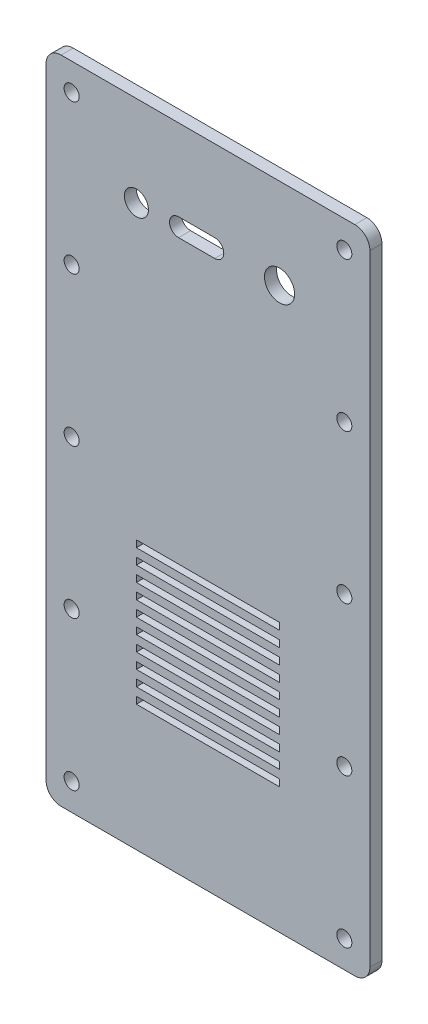
SolidWorks part; units mm, degrees
ref_plane "Front Plane" through (0, 0, 0) normal (0, 0, 1) x (1, 0, 0)
ref_plane "Top Plane" through (0, 0, 0) normal (0, 1, 0) x (1, 0, 0)
ref_plane "Right Plane" through (0, 0, 0) normal (1, 0, 0) x (0, 0, -1)
sketch "Sketch1" plane through (0, 0, 0) normal (0, 0, 1) x (1, 0, 0)
  line L1 (-17.88, -45) -> (17.88, -45) construction
  line L2 (-17.88, -45) -> (-17.88, 45) construction
  line L3 (-17.88, 45) -> (17.88, 45) construction
  line L4 (17.88, -45) -> (17.88, 45) construction
  line L5 (-17.88, -45) -> (17.88, 45) construction
  line L6 (-17.88, 45) -> (17.88, -45) construction
  line L7 (-26.88, 54) -> (26.88, 54)
  line L8 (-26.88, 54) -> (-26.88, -54)
  line L9 (-26.88, -54) -> (26.88, -54)
  line L10 (26.88, 54) -> (26.88, -54)
  line L11 (-26.88, 54) -> (26.88, -54) construction
  line L12 (-26.88, -54) -> (26.88, 54) construction
  point P0 (0, 0)
  point P6 (0, 0)
  dimension "D1" = 90
  dimension "D2" = 35.76
  dimension "D3" = 9
  dimension "D4" = 9
extrude "Boss-Extrude1" add sketch "Sketch1" along normal blind 2
fillet "Fillet1" radius 2.5 4 edges at (-26.88, -54, 1) (26.88, -54, 1) (-26.88, 54, 1) (26.88, 54, 1)
sketch "Sketch2" plane through (0, 0, 2) normal (0, 0, 1) x (1, 0, 0)
  line L0 (-17.88, -45) -> (-17.88, 45) construction
  line L1 (-22.63, -49.5) -> (22.63, -49.5) construction
  line L2 (-22.63, -49.5) -> (-22.63, 49.5) construction
  line L3 (-22.63, 49.5) -> (22.63, 49.5) construction
  line L4 (22.63, -49.5) -> (22.63, 49.5) construction
  line L5 (-22.63, -49.5) -> (22.63, 49.5) construction
  line L6 (-22.63, 49.5) -> (22.63, -49.5) construction
  circle A0 centre (-22.63, 49.5) radius 1.25
  circle A1 centre (22.63, 49.5) radius 1.25
  circle A2 centre (22.63, 24.75) radius 1.25
  circle A3 centre (22.63, 0) radius 1.25
  circle A4 centre (22.63, -24.75) radius 1.25
  circle A5 centre (22.63, -49.5) radius 1.25
  circle A6 centre (-22.63, 24.75) radius 1.25
  circle A7 centre (-22.63, 0) radius 1.25
  circle A8 centre (-22.63, -24.75) radius 1.25
  circle A9 centre (-22.63, -49.5) radius 1.25
  point P0 (0, 0)
  dimension "D3" = 2.5
  dimension "D1" = 4.75
  dimension "D2" = 99
  dimension "D4" = 5
extrude "Cut-Extrude1" cut sketch "Sketch2" against normal up to surface (2 mm away) up to face at (0, 0, 0)
sketch "Sketch3" plane through (0, 0, 2) normal (0, 0, 1) x (1, 0, 0)
  line L0 (-4.88, 39) -> (1.12, 39) construction
  line L1 (-4.88, 40.5) -> (1.12, 40.5)
  line L2 (-4.88, 37.5) -> (1.12, 37.5)
  line L3 (24.38, 54) -> (-24.38, 54) construction
  line L4 (-26.88, 51.5) -> (-26.88, -51.5) construction
  line L5 (26.88, -51.5) -> (26.88, 51.5) construction
  line L6 (-11.88, -13.0694) -> (-11.88, -11.9306)
  line L7 (-11.88, -10.5694) -> (11.88, -10.5694)
  line L8 (-11.88, -10.5694) -> (-11.88, -9.4306)
  line L9 (-11.88, -9.4306) -> (11.88, -9.4306)
  line L10 (11.88, -10.5694) -> (11.88, -9.4306)
  line L11 (-11.88, -10.5694) -> (11.88, -9.4306) construction
  line L12 (-11.88, -9.4306) -> (11.88, -10.5694) construction
  line L13 (-11.88, -13.0694) -> (11.88, -13.0694)
  line L14 (11.88, -13.0694) -> (11.88, -11.9306)
  line L15 (-11.88, -11.9306) -> (11.88, -11.9306)
  line L16 (-11.88, -15.5694) -> (-11.88, -14.4306)
  line L17 (-11.88, -15.5694) -> (11.88, -15.5694)
  line L18 (11.88, -15.5694) -> (11.88, -14.4306)
  line L19 (-11.88, -14.4306) -> (11.88, -14.4306)
  line L20 (-11.88, -18.0694) -> (-11.88, -16.9306)
  line L21 (-11.88, -18.0694) -> (11.88, -18.0694)
  line L22 (11.88, -18.0694) -> (11.88, -16.9306)
  line L23 (-11.88, -16.9306) -> (11.88, -16.9306)
  line L24 (-11.88, -20.5694) -> (-11.88, -19.4306)
  line L25 (-11.88, -20.5694) -> (11.88, -20.5694)
  line L26 (11.88, -20.5694) -> (11.88, -19.4306)
  line L27 (-11.88, -19.4306) -> (11.88, -19.4306)
  line L28 (-11.88, -23.0694) -> (-11.88, -21.9306)
  line L29 (-11.88, -23.0694) -> (11.88, -23.0694)
  line L30 (11.88, -23.0694) -> (11.88, -21.9306)
  line L31 (-11.88, -21.9306) -> (11.88, -21.9306)
  line L32 (-11.88, -25.5694) -> (-11.88, -24.4306)
  line L33 (-11.88, -25.5694) -> (11.88, -25.5694)
  line L34 (11.88, -25.5694) -> (11.88, -24.4306)
  line L35 (-11.88, -24.4306) -> (11.88, -24.4306)
  line L36 (-11.88, -28.0694) -> (-11.88, -26.9306)
  line L37 (-11.88, -28.0694) -> (11.88, -28.0694)
  line L38 (11.88, -28.0694) -> (11.88, -26.9306)
  line L39 (-11.88, -26.9306) -> (11.88, -26.9306)
  line L40 (-11.88, -30.5694) -> (-11.88, -29.4306)
  line L41 (-11.88, -30.5694) -> (11.88, -30.5694)
  line L42 (11.88, -30.5694) -> (11.88, -29.4306)
  line L43 (-11.88, -29.4306) -> (11.88, -29.4306)
  line L44 (-11.88, -33.0694) -> (-11.88, -31.9306)
  line L45 (-11.88, -33.0694) -> (11.88, -33.0694)
  line L46 (11.88, -33.0694) -> (11.88, -31.9306)
  line L47 (-11.88, -31.9306) -> (11.88, -31.9306)
  circle A0 centre (11.88, 39) radius 2.5
  circle A1 centre (-11.88, 39) radius 2
  arc A2 (-4.88, 40.5) -> (-4.88, 37.5) centre (-4.88, 39) ccw
  arc A3 (1.12, 37.5) -> (1.12, 40.5) centre (1.12, 39) ccw
  point P6 (-1.88, 39)
  point P11 (-1.88, 37.5)
  point P21 (0, -10)
  dimension "D1" = 5
  dimension "D2" = 4
  dimension "D3" = 6
  dimension "D4" = 3
  dimension "D5" = 15
  dimension "D6" = 15
  dimension "D7" = 10
  dimension "D8" = 15
  dimension "D9" = 1.1389
  dimension "D10" = 15
  dimension "D11" = 10
  dimension "D13" = 2.5
  dimension "D12" = 10
extrude "Cut-Extrude2" cut sketch "Sketch3" against normal up to surface (2 mm away) up to face at (23.88, -49.5, 0)
equation "\"case_width\"=35.76"
equation "\"D2@Sketch1\"=\"case_width\""
